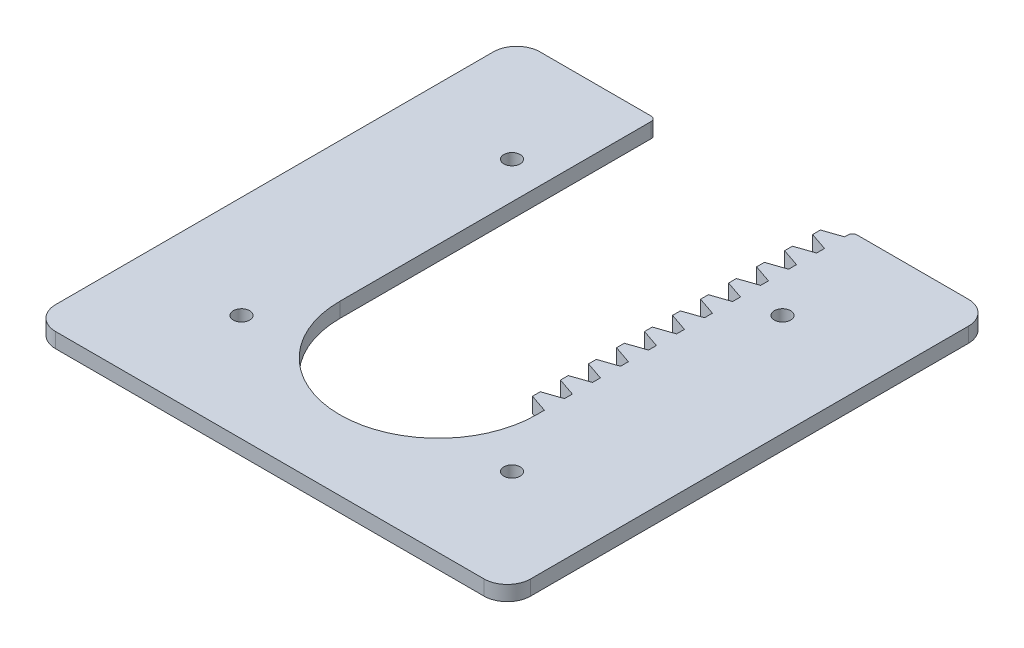
SolidWorks part; units mm, degrees
ref_plane "Front Plane" through (0, 0, 0) normal (0, 0, 1) x (1, 0, 0)
ref_plane "Top Plane" through (0, 0, 0) normal (0, 1, 0) x (1, 0, 0)
ref_plane "Right Plane" through (0, 0, 0) normal (1, 0, 0) x (0, 0, -1)
sketch "Sketch1" plane through (0, 0, 0) normal (0, 1, 0) x (1, 0, 0)
  line L0 (0, 0) -> (0, 21) construction
  line L1 (17.1887, 0) -> (0, 0) construction
  line L2 (21.0585, 3.843) -> (17.1887, 5.1665) construction
  line L3 (17.1887, 5.1665) -> (17.1887, 6.8335) construction
  line L4 (17.1887, 6.8335) -> (21.0585, 8.157) construction
  line L5 (21.0585, 9.843) -> (21.0585, 8.157) construction
  line L6 (21.0585, 9.843) -> (17.1887, 11.1665) construction
  line L7 (17.1887, 11.1665) -> (17.1887, 12.8335) construction
  line L8 (17.1887, 12.8335) -> (21.0585, 14.157) construction
  line L9 (21.0585, 15.843) -> (21.0585, 14.157) construction
  line L10 (21.0585, 15.843) -> (17.1887, 17.1665) construction
  line L11 (17.1887, 17.1665) -> (17.1887, 18.8335) construction
  line L12 (17.1887, 18.8335) -> (21.0585, 20.157) construction
  line L13 (21.0585, 21.843) -> (21.0585, 20.157) construction
  line L14 (21.0585, 21.843) -> (17.1887, 23.1665) construction
  line L15 (17.1887, 23.1665) -> (17.1887, 24.8335) construction
  line L16 (17.1887, 24.8335) -> (21.0585, 26.157) construction
  line L17 (21.0585, 27.843) -> (21.0585, 26.157) construction
  line L18 (21.0585, 27.843) -> (17.1887, 29.1665) construction
  line L19 (17.1887, 29.1665) -> (17.1887, 30.8335) construction
  line L20 (17.1887, 30.8335) -> (21.0585, 32.157) construction
  line L21 (21.0585, 33.843) -> (21.0585, 32.157) construction
  line L22 (21.0585, 33.843) -> (17.1887, 35.1665) construction
  line L23 (17.1887, 35.1665) -> (17.1887, 36.8335) construction
  line L24 (17.1887, 36.8335) -> (21.0585, 38.157) construction
  line L25 (21.0585, 39.843) -> (21.0585, 38.157) construction
  line L26 (21.0585, 39.843) -> (17.1887, 41.1665) construction
  line L27 (17.1887, 41.1665) -> (17.1887, 42.8335) construction
  line L28 (17.1887, 42.8335) -> (21.0585, 44.157) construction
  line L29 (21.0585, 45.843) -> (21.0585, 44.157) construction
  line L30 (21.0585, 45.843) -> (17.1887, 47.1665) construction
  line L31 (17.1887, 47.1665) -> (17.1887, 48.8335) construction
  line L32 (17.1887, 48.8335) -> (21.0585, 50.157) construction
  line L33 (21.0585, 51.843) -> (21.0585, 50.157) construction
  line L34 (21.0585, 51.843) -> (17.1887, 53.1665) construction
  line L35 (17.1887, 53.1665) -> (17.1887, 54.8335) construction
  line L36 (17.1887, 54.8335) -> (21.0585, 56.157) construction
  line L37 (21.0585, 57.843) -> (21.0585, 56.157) construction
  line L38 (21.0585, 57.843) -> (17.1887, 59.1665) construction
  line L39 (17.1887, 59.1665) -> (17.1887, 60.8335) construction
  line L40 (17.1887, 60.8335) -> (21.0585, 62.157) construction
  line L41 (21.0585, 62.157) -> (21.0585, 62.843) construction
  line L42 (45.8722, 63.843) -> (22.0585, 63.843) construction
  line L43 (50.8722, -34.9014) -> (50.8722, 58.843) construction
  line L44 (45.8722, -39.9014) -> (-45.8722, -39.9014) construction
  line L45 (-50.8722, 58.843) -> (-50.8722, -34.9014) construction
  line L46 (-45.8722, 63.843) -> (-22.0585, 63.843) construction
  line L47 (-21.0585, -3.843) -> (-21.0585, 62.843) construction
  line L48 (21.0585, -2.157) -> (21.0585, -3.843) construction
  line L49 (21.0585, -2.157) -> (17.1887, -0.8335) construction
  line L50 (17.1887, -0.8335) -> (17.1887, 0.8335) construction
  line L51 (17.1887, 0.8335) -> (21.0585, 2.157) construction
  line L52 (21.0585, 3.843) -> (21.0585, 2.157) construction
  line L53 (21.0585, 3.843) -> (17.1887, 5.1665)
  line L54 (17.1887, 5.1665) -> (17.1887, 6.8335)
  line L55 (17.1887, 6.8335) -> (21.0585, 8.157)
  line L56 (21.0585, 9.843) -> (21.0585, 8.157)
  line L57 (21.0585, 9.843) -> (17.1887, 11.1665)
  line L58 (17.1887, 11.1665) -> (17.1887, 12.8335)
  line L59 (17.1887, 12.8335) -> (21.0585, 14.157)
  line L60 (21.0585, 15.843) -> (21.0585, 14.157)
  line L61 (21.0585, 15.843) -> (17.1887, 17.1665)
  line L62 (17.1887, 17.1665) -> (17.1887, 18.8335)
  line L63 (17.1887, 18.8335) -> (21.0585, 20.157)
  line L64 (21.0585, 21.843) -> (21.0585, 20.157)
  line L65 (21.0585, 21.843) -> (17.1887, 23.1665)
  line L66 (17.1887, 23.1665) -> (17.1887, 24.8335)
  line L67 (17.1887, 24.8335) -> (21.0585, 26.157)
  line L68 (21.0585, 27.843) -> (21.0585, 26.157)
  line L69 (21.0585, 27.843) -> (17.1887, 29.1665)
  line L70 (17.1887, 29.1665) -> (17.1887, 30.8335)
  line L71 (17.1887, 30.8335) -> (21.0585, 32.157)
  line L72 (21.0585, 33.843) -> (21.0585, 32.157)
  line L73 (21.0585, 33.843) -> (17.1887, 35.1665)
  line L74 (17.1887, 35.1665) -> (17.1887, 36.8335)
  line L75 (17.1887, 36.8335) -> (21.0585, 38.157)
  line L76 (21.0585, 39.843) -> (21.0585, 38.157)
  line L77 (21.0585, 39.843) -> (17.1887, 41.1665)
  line L78 (17.1887, 41.1665) -> (17.1887, 42.8335)
  line L79 (17.1887, 42.8335) -> (21.0585, 44.157)
  line L80 (21.0585, 45.843) -> (21.0585, 44.157)
  line L81 (21.0585, 45.843) -> (17.1887, 47.1665)
  line L82 (17.1887, 47.1665) -> (17.1887, 48.8335)
  line L83 (17.1887, 48.8335) -> (21.0585, 50.157)
  line L84 (21.0585, 51.843) -> (21.0585, 50.157)
  line L85 (21.0585, 51.843) -> (17.1887, 53.1665)
  line L86 (17.1887, 53.1665) -> (17.1887, 54.8335)
  line L87 (17.1887, 54.8335) -> (21.0585, 56.157)
  line L88 (21.0585, 57.843) -> (21.0585, 56.157)
  line L89 (21.0585, 57.843) -> (17.1887, 59.1665)
  line L90 (17.1887, 59.1665) -> (17.1887, 60.8335)
  line L91 (17.1887, 60.8335) -> (21.0585, 62.157)
  line L92 (21.0585, 62.157) -> (21.0585, 62.843)
  line L93 (45.8722, 63.843) -> (22.0585, 63.843)
  line L94 (50.8722, -34.9014) -> (50.8722, 58.843)
  line L95 (45.8722, -39.9014) -> (-45.8722, -39.9014)
  line L96 (-50.8722, 58.843) -> (-50.8722, -34.9014)
  line L97 (-45.8722, 63.843) -> (-22.0585, 63.843)
  line L98 (-21.0585, -3.843) -> (-21.0585, 62.843)
  line L99 (21.0585, -2.157) -> (21.0585, -3.843)
  line L100 (21.0585, -2.157) -> (17.1887, -0.8335)
  line L101 (17.1887, -0.8335) -> (17.1887, 0.8335)
  line L102 (17.1887, 0.8335) -> (21.0585, 2.157)
  line L103 (21.0585, 3.843) -> (21.0585, 2.157)
  line L104 (0, 63.843) -> (0, -39.9014) construction
  line L105 (-51.8722, 11.9708) -> (51.8722, 11.9708) construction
  line L106 (0, 11.9708) -> (-51.8722, -39.9014) construction
  line L107 (51.8722, -24.9014) -> (-51.8722, -24.9014) construction
  line L108 (-36.8722, -39.9014) -> (-36.8722, 63.843) construction
  line L109 (36.8722, -39.9014) -> (36.8722, 63.843) construction
  line L110 (45.8722, -39.9014) -> (51.8722, -39.9014) construction
  line L111 (51.8722, -39.9014) -> (51.8722, 63.843) construction
  line L112 (51.8722, 63.843) -> (-51.8722, 63.843) construction
  line L113 (17.1887, 60) -> (0, 60) construction
  line L114 (-51.8722, 63.843) -> (-51.8722, -39.9014) construction
  line L115 (-51.8722, -39.9014) -> (-45.8722, -39.9014) construction
  circle A0 centre (0, 0) radius 21 construction
  circle A1 centre (0, 60) radius 21 construction
  arc A2 (22.0585, 63.843) -> (21.0585, 62.843) centre (22.0585, 62.843) ccw construction
  arc A3 (50.8722, 58.843) -> (45.8722, 63.843) centre (45.8722, 58.843) ccw construction
  arc A4 (45.8722, -39.9014) -> (50.8722, -34.9014) centre (45.8722, -34.9014) ccw construction
  arc A5 (-50.8722, -34.9014) -> (-45.8722, -39.9014) centre (-45.8722, -34.9014) ccw construction
  arc A6 (-45.8722, 63.843) -> (-50.8722, 58.843) centre (-45.8722, 58.843) ccw construction
  arc A7 (-21.0585, 62.843) -> (-22.0585, 63.843) centre (-22.0585, 62.843) ccw construction
  arc A8 (-21.0585, -3.843) -> (21.0585, -3.843) centre (0, -3.843) ccw construction
  arc A9 (22.0585, 63.843) -> (21.0585, 62.843) centre (22.0585, 62.843) ccw
  arc A10 (50.8722, 58.843) -> (45.8722, 63.843) centre (45.8722, 58.843) ccw
  arc A11 (45.8722, -39.9014) -> (50.8722, -34.9014) centre (45.8722, -34.9014) ccw
  arc A12 (-50.8722, -34.9014) -> (-45.8722, -39.9014) centre (-45.8722, -34.9014) ccw
  arc A13 (-45.8722, 63.843) -> (-50.8722, 58.843) centre (-45.8722, 58.843) ccw
  arc A14 (-21.0585, 62.843) -> (-22.0585, 63.843) centre (-22.0585, 62.843) ccw
  arc A15 (-21.0585, -3.843) -> (21.0585, -3.843) centre (0, -3.843) ccw
  circle A16 centre (28.9653, -16.9946) radius 1.75 construction
  circle A17 centre (-28.9653, -16.9946) radius 1.75 construction
  circle A18 centre (-28.9653, 40.9361) radius 1.75 construction
  circle A19 centre (28.9653, 40.9361) radius 1.75 construction
  circle A20 centre (28.9653, -16.9946) radius 1.75
  circle A21 centre (-28.9653, -16.9946) radius 1.75
  circle A22 centre (-28.9653, 40.9361) radius 1.75
  circle A23 centre (28.9653, 40.9361) radius 1.75
  circle A24 centre (0, 60) radius 21 construction
sketch "Sketch2" plane through (0, 0, 0) normal (0, 0, 1) x (1, 0, 0)
  line L0 (0, 0) -> (0, 3.2) construction
  line L1 (-50.8722, 0) -> (50.8722, 0)
  line L2 (-50.8722, 0) -> (-50.8722, 3.2)
  line L3 (-50.8722, 3.2) -> (50.8722, 3.2)
  line L4 (50.8722, 0) -> (50.8722, 3.2)
  line L5 (-50.8722, 3.2) -> (-51.8722, 3.2) construction
  line L6 (-51.8722, 3.2) -> (-51.8722, 4.2) construction
  line L7 (-51.8722, 4.2) -> (51.8722, 4.2) construction
  line L8 (51.8722, 4.2) -> (51.8722, 3.2) construction
  line L9 (51.8722, 3.2) -> (50.8722, 3.2) construction
  line L10 (50.8722, 0) -> (51.8722, 0) construction
  line L11 (51.8722, 0) -> (51.8722, -1) construction
  line L12 (51.8722, -1) -> (-51.8722, -1) construction
  line L13 (-51.8722, -1) -> (-51.8722, 0) construction
  line L14 (-51.8722, 0) -> (-50.8722, 0) construction
  dimension "D1" = 3.2
  dimension "D2" = 1
extrude "Boss-Extrude1" add sketch "Sketch1" along normal up to vertex (3.2 mm away) up to point (-50.8722, 3.2, 0)
ref_plane "edge" through (0, 0, -63.843) normal (0, 0, 1) x (1, 0, 0)
